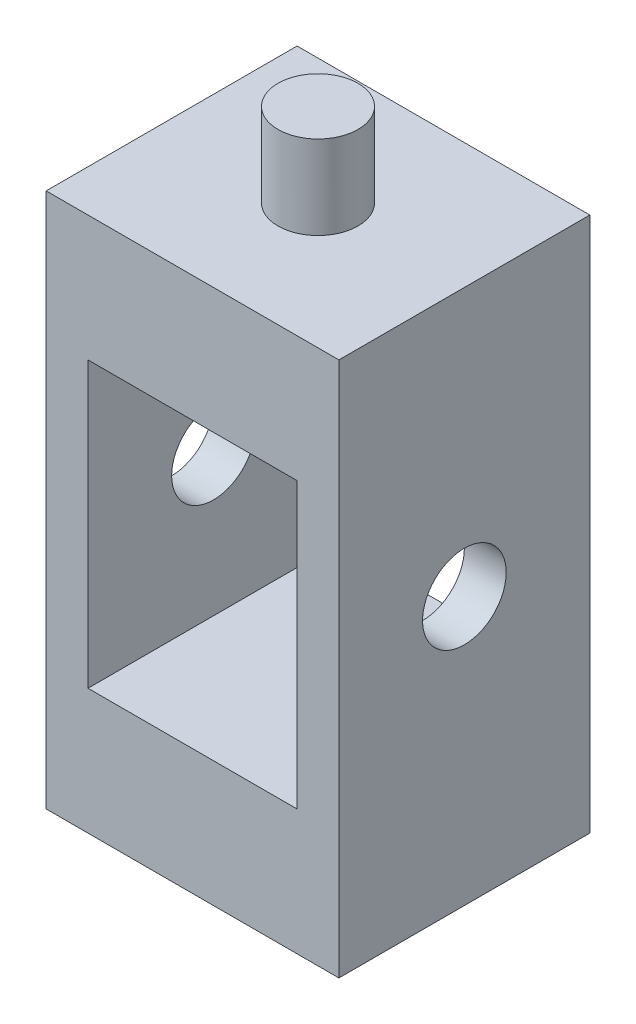
SolidWorks part; units mm, degrees
material "1060 合金"
ref_plane "前视基准面" through (0, 0, 0) normal (0, 0, 1) x (1, 0, 0)
ref_plane "上视基准面" through (0, 0, 0) normal (0, 1, 0) x (1, 0, 0)
ref_plane "右视基准面" through (0, 0, 0) normal (1, 0, 0) x (0, 0, -1)
sketch "草图1" plane through (0, 0, 0) normal (0, 0, 1) x (1, 0, 0)
  line L0 (0, 0) -> (0, 15) construction
  line L1 (-17.5, -20) -> (17.5, -20)
  line L2 (-17.5, -20) -> (-17.5, 20)
  line L3 (-17.5, 20) -> (-12.5, 20)
  line L4 (17.5, -20) -> (17.5, 20)
  line L5 (-17.5, -20) -> (17.5, 20) construction
  line L6 (-17.5, 20) -> (17.5, -20) construction
  line L7 (12.5, 20) -> (17.5, 20)
  line L8 (-12.5, -5) -> (12.5, -5)
  line L9 (-12.5, -5) -> (-12.5, 20)
  line L11 (12.5, -5) -> (12.5, 20)
  line L12 (-12.5, -5) -> (12.5, 20) construction
  line L13 (-12.5, 20) -> (12.5, -5) construction
  point P0 (0, 0)
  point P8 (0, 7.5)
  dimension "D1" = 25
  dimension "D2" = 5
  dimension "D3" = 15
  dimension "D4" = 25
extrude "凸台-拉伸1" add sketch "草图1" along normal mid plane 30
sketch "草图2" plane through (17.5, 0, 0) normal (1, 0, 0) x (0, 0, -1)
  line L0 (0, 0) -> (0, 20) construction
  line L3 (-15, 20) -> (15, 20) construction
  circle A0 centre (0, 12) radius 5
  dimension "D1" = 10
  dimension "D2" = 8
extrude "切除-拉伸1" cut sketch "草图2" against normal through all
sketch "草图3" plane through (0, -20, 0) normal (0, -1, 0) x (1, 0, 0)
  circle A0 centre (0, 0) radius 4.7811
extrude "凸台-拉伸2" add sketch "草图3" along normal blind 10
ref_plane "基准面1" through (0, 12, 0) normal (0, 1, 0) x (1, 0, 0)
mirror "镜向1" about plane through (0, 12, 0) normal (0, 1, 0) of "切除-拉伸1", "凸台-拉伸1", "凸台-拉伸2"
